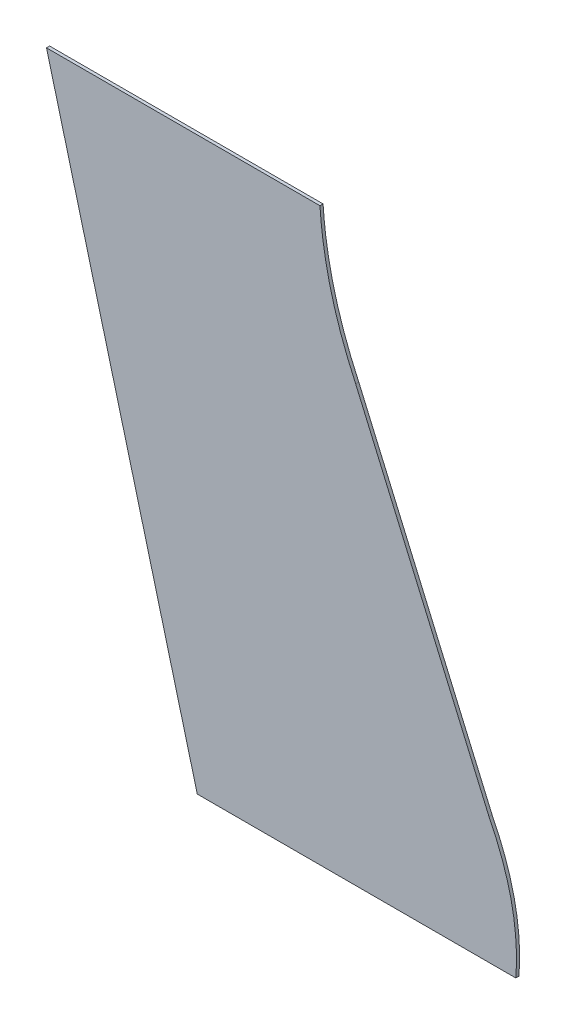
SolidWorks part; units mm, degrees
ref_plane "Front Plane" through (0, 0, 0) normal (0, 0, 1) x (1, 0, 0)
ref_plane "Top Plane" through (0, 0, 0) normal (0, 1, 0) x (1, 0, 0)
ref_plane "Right Plane" through (0, 0, 0) normal (1, 0, 0) x (0, 0, -1)
sketch "Sketch1" plane through (0, 0, 0) normal (0, 0, 1) x (1, 0, 0)
  line L0 (275.2156, 1168.292) -> (1376.0774, 1168.292) construction
  line L25 (2039.2075, -617.8057) -> (2167.619, -914.5593)
  line L26 (2193.4612, -1036.3301) -> (1886.6112, -1036.317)
  line L27 (1886.6112, -1036.317) -> (1741.3194, -486.3143)
  line L51 (1741.3194, -486.3143) -> (2004.8065, -486.3143)
  spline S3 degree 2 poles (2167.619, -914.5593) (2198.3193, -975.3516) (2193.4612, -1036.3301) knots 0 0 0 0.705421 0.705421 0.705421
  spline S5 degree 2 poles (2039.2075, -617.8057) (2009.1335, -553.5013) (2004.8065, -486.3143) knots 0 0 0 0.662343 0.662343 0.662343
  dimension "D1" = 550.0026
  dimension "D2" = 306.85
  dimension "D3" = 263.4871
  dimension "D4" = 296.7536
extrude "Boss-Extrude1" add sketch "Sketch1" along normal blind 3 contours S5 L51 L27 L26 S3 L25
